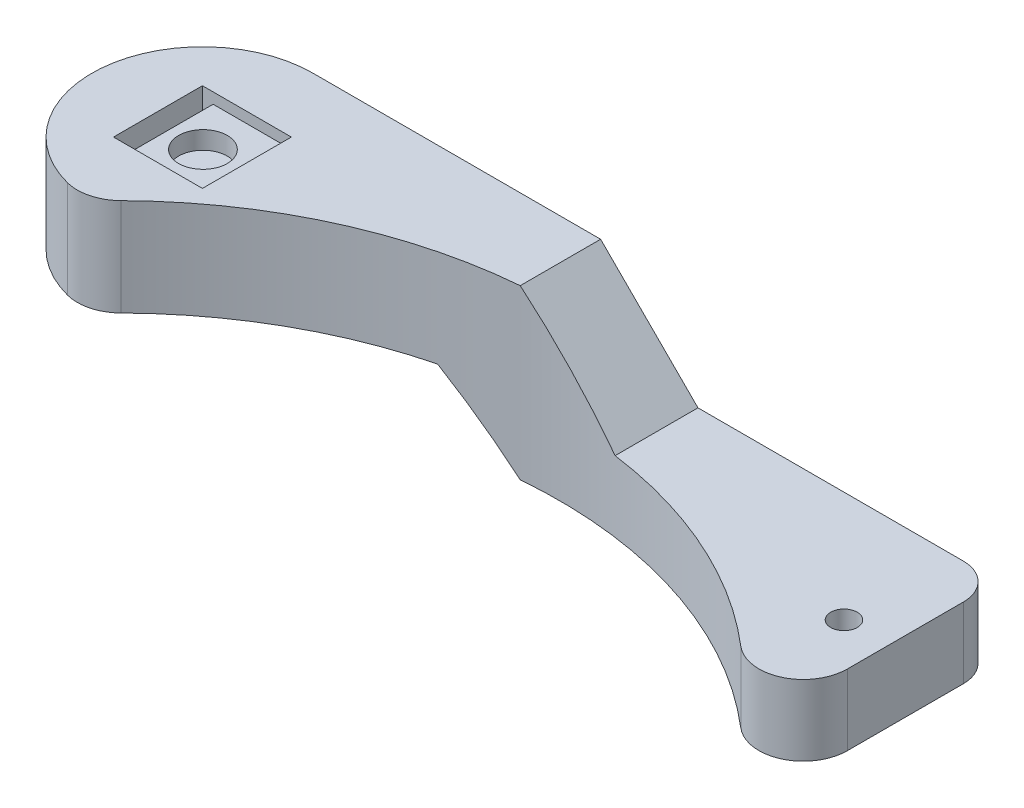
SolidWorks part; units mm, degrees
ref_plane "Front Plane" through (0, 0, 0) normal (0, 0, 1) x (1, 0, 0)
ref_plane "Top Plane" through (0, 0, 0) normal (0, 1, 0) x (1, 0, 0)
ref_plane "Right Plane" through (0, 0, 0) normal (1, 0, 0) x (0, 0, -1)
sketch "Sketch1" plane through (0, 0, 0) normal (0, 1, 0) x (1, 0, 0)
  line L1 (-45, 12.5) -> (45, 12.5)
  line L2 (-45, 12.5) -> (-45, -12.5)
  line L3 (-45, -12.5) -> (45, -12.5)
  line L4 (45, 12.5) -> (45, -12.5)
  dimension "D1" = 90
  dimension "D2" = 45
  dimension "D3" = 25
  dimension "D4" = 12.5
extrude "Boss-Extrude1" add sketch "Sketch1" along normal blind 19
sketch "Sketch3" plane through (0, 19, 0) normal (0, 1, 0) x (1, 0, 0)
  line L0 (-45, 12.5) -> (-45, -12.5) construction
  line L1 (-37.525, 5.025) -> (-27.475, 5.025)
  line L2 (-37.525, 5.025) -> (-37.525, -5.025)
  line L3 (-37.525, -5.025) -> (-27.475, -5.025)
  line L4 (-27.475, 5.025) -> (-27.475, -5.025)
  line L7 (-45, -12.5) -> (45, -12.5) construction
  point P4 (-32.5, 5.025)
  point P6 (-27.475, 0)
  dimension "D1" = 10.05
  dimension "D2" = 10.05
  dimension "D3" = 12.5
  dimension "D4" = 12.5
extrude "Cut-Extrude2" cut sketch "Sketch3" against normal blind 1.21
sketch "Sketch4" plane through (0, 17.79, 0) normal (0, 1, 0) x (1, 0, 0)
  line L0 (-28.685, 5.025) -> (-28.685, -5.025)
  line L1 (-27.475, 5.025) -> (-37.525, 5.025) construction
  line L2 (-37.525, -5.025) -> (-27.475, -5.025) construction
  line L3 (-28.685, -5.025) -> (-27.475, -5.025)
  line L4 (-27.475, -5.025) -> (-27.475, 5.025)
  line L5 (-27.475, 5.025) -> (-28.685, 5.025)
  line L6 (-37.525, 5.025) -> (-36.315, 5.025)
  line L7 (-36.315, 5.025) -> (-36.315, -5.025)
  line L8 (-36.315, -5.025) -> (-37.525, -5.025)
  line L9 (-37.525, -5.025) -> (-37.525, 5.025)
  dimension "D1" = 1.21
  dimension "D2" = 1.21
extrude "Cut-Extrude3" cut sketch "Sketch4" against normal blind 2.02
sketch "Sketch5" plane through (0, 17.79, 0) normal (0, 1, 0) x (1, 0, 0)
  line L0 (-28.685, 5.025) -> (-28.685, -5.025) construction
  line L1 (-27.475, 5.025) -> (-37.525, 5.025) construction
  circle A0 centre (-32.465, 0.025) radius 2.75
  dimension "D3" = 5.5
  dimension "D1" = 3.78
  dimension "D2" = 5
extrude "Cut-Extrude4" cut sketch "Sketch5" against normal blind 2.02
sketch "Esquisse2" plane through (0, 0, 12.5) normal (0, 0, 1) x (1, 0, 0)
  line L0 (0, 19) -> (11, 8)
  line L1 (45, 19) -> (0, 19)
  line L2 (45, 19) -> (45, 8)
  line L3 (45, 8) -> (0, 8)
  line L4 (0, 19) -> (0, 8)
  line L5 (-45, 0) -> (0, 0)
  line L6 (-45, 0) -> (-45, 8)
  line L7 (-45, 8) -> (0, 8)
  line L8 (0, 0) -> (0, 8)
  line L9 (0, 0) -> (-8, 8)
  line M3 (-45, 0) -> (45, 0)
  line M4 (45, 0) -> (45, 19)
  line M5 (45, 19) -> (-45, 19)
  line M6 (-45, 19) -> (-45, 0)
  dimension "D1" = 45
  dimension "D2" = 11
  dimension "D3" = 45
  dimension "D4" = 45
extrude "Enlèv. mat.-Extru.1" cut sketch "Esquisse2" against normal blind 34 contours L8 L7 M3 M6 | L4 L3 M5 M4 region at (25.1224, 13.7553, 12.5) region at (-24.435, 3.8699, 12.5)
fillet "Fillet1" 2 edges at (-45, 13.5, 12.5) (-45, 13.5, -12.5) type full round first side face at (0.375, 8.75, 12.5) second side face at (0.375, 8.75, -12.5) middle face at (-45, 13.5, 0)
sketch "Esquisse3" plane through (0, 8, 0) normal (0, -1, 0) x (1, 0, 0)
  circle A0 centre (-32.5, 0) radius 6.96
  dimension "D1" = 13.92
extrude "Enlèv. mat.-Extru.2" cut sketch "Esquisse3" against normal blind 1.1
sketch "Esquisse4" plane through (0, 9.1, 0) normal (0, -1, 0) x (1, 0, 0)
  circle A0 centre (-32.5, 0) radius 6.4
  dimension "D1" = 12.8
extrude "Enlèv. mat.-Extru.3" cut sketch "Esquisse4" against normal blind 3.6
sketch "Esquisse5" plane through (0, 0, 0) normal (0, -1, 0) x (-1, 0, 0)
  line L0 (-45, -12.5) -> (-45, 12.5) construction
  circle A0 centre (-40, 0) radius 1.5
  dimension "D2" = 3
  dimension "D1" = 5
extrude "Enlèv. mat.-Extru.4" cut sketch "Esquisse5" against normal through all
fillet "Fillet3" radius 4 2 edges at (45, 4, -12.5) (45, 4, 12.5)
sketch "Esquisse10" plane through (0, 8, 0) normal (0, -1, 0) x (1, 0, 0)
  point P0 (-32.5, 12.5)
sketch "Esquisse12" plane through (0, 0, 12.5) normal (0, 0, 1) x (1, 0, 0)
  line L0 (-32.5, 8) -> (-32.5, 0) construction
  dimension "D1" = 0
sketch "Esquisse13" plane through (0, 0, 0) normal (0, -1, 0) x (1, 0, 0)
  circle A0 centre (4.25, 46.4034) radius 50
  dimension "D1" = 100
extrude "Enlèv. mat.-Extru.6" cut sketch "Esquisse13" against normal through all
fillet "Congé3" radius 5 2 edges at (-32.5, 13.5, 12.5) (41, 4, 12.5)
